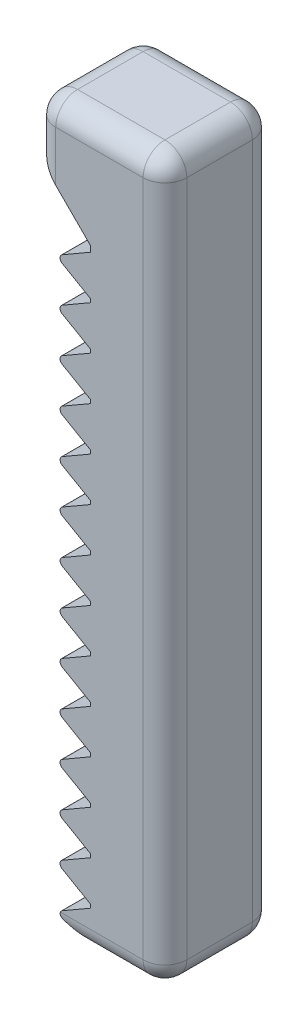
SolidWorks part; units mm, degrees
ref_plane "Front" through (0, 0, 0) normal (0, 0, 1) x (1, 0, 0)
ref_plane "Top" through (0, 0, 0) normal (0, 1, 0) x (1, 0, 0)
ref_plane "Right" through (0, 0, 0) normal (1, 0, 0) x (0, 0, -1)
sketch "Sketch1" plane through (0, 0, 0) normal (0, 1, 0) x (1, 0, 0)
  line L1 (-3, -2.5) -> (3, -2.5)
  line L2 (-3, -2.5) -> (-3, 2.5)
  line L3 (-3, 2.5) -> (3, 2.5)
  line L4 (3, -2.5) -> (3, 2.5)
  line L5 (-3, -2.5) -> (3, 2.5) construction
  line L6 (-3, 2.5) -> (3, -2.5) construction
  point P0 (0, 0)
  dimension "D1" = 5
  dimension "D2" = 6
extrude "Boss-Extrude1" add sketch "Sketch1" along normal blind 33
sketch "Sketch2" plane through (0, 0, -2.5) normal (0, 0, -1) x (-1, 0, 0)
  line L0 (3, 33) -> (3, 0) construction
  line L2 (3, 2.5) -> (3, 30.7)
  line L3 (3, 30.7) -> (0.4, 28.1)
  line L4 (0.4, 5.1) -> (0.4, 28.1)
  line L5 (3, 2.5) -> (0.4, 5.1) construction
  line L6 (-3, 0) -> (3, 0) construction
  line L7 (0.4, 5.1) -> (0.4, 0)
  line L8 (0.4, 0) -> (3, 0)
  line L9 (3, 0) -> (3, 2.5)
  dimension "D1" = 45
  dimension "D2" = 23
  dimension "D3" = 2.6
  dimension "D4" = 2.5
  dimension "D5" = 45
extrude "Cut-Extrude1" cut sketch "Sketch2" against normal through all both and the other way through all
sketch "Sketch3" plane through (0, 0, -2.5) normal (0, 0, -1) x (-1, 0, 0)
  line L0 (0.4, 0) -> (1.7, 0.7506)
  line L1 (1.7, 1.097) -> (0.4, 1.8475)
  line L2 (0.4, 0) -> (0.4, 28.1) construction
  line L3 (0.4, 1.8475) -> (0.4, 0)
  line L4 (1.7, 1.097) -> (2, 0.9238) construction
  line L5 (2, 0.9238) -> (1.7, 0.7506) construction
  line L6 (0.4, 0) -> (0.4, 28.1) construction
  line L7 (-3, 0) -> (0.4, 0) construction
  arc A0 (1.7, 0.7506) -> (1.7, 1.097) centre (1.6, 0.9238) ccw
  point P3 (0.4, 5.1)
  point P7 (0.4, 0)
  point P12 (0.4, 0)
  dimension "D1" = 0.2
  dimension "D2" = 60
  dimension "D3" = 1.6
extrude "Boss-Extrude2" add sketch "Sketch3" against normal up to surface (5 mm away) up to face at (-0.1333, 20.8, 2.5)
pattern_linear "LPattern1" count 14 spacing 2 along (0, 1, 0) of "Boss-Extrude2"
fillet "Fillet1" radius 1 13 edges at (1.3, 0, -2.5) (1.3, 0, 2.5) (-3, 33, 0) (-3, 31.85, 2.5) (-3, 30.7, 0) (-3, 31.85, -2.5) (3, 16.5, 2.5) (3, 33, 0) (3, 16.5, -2.5) (3, 0, 0) (0, 33, 2.5) (0, 33, -2.5) (-0.4, 0, 0)
